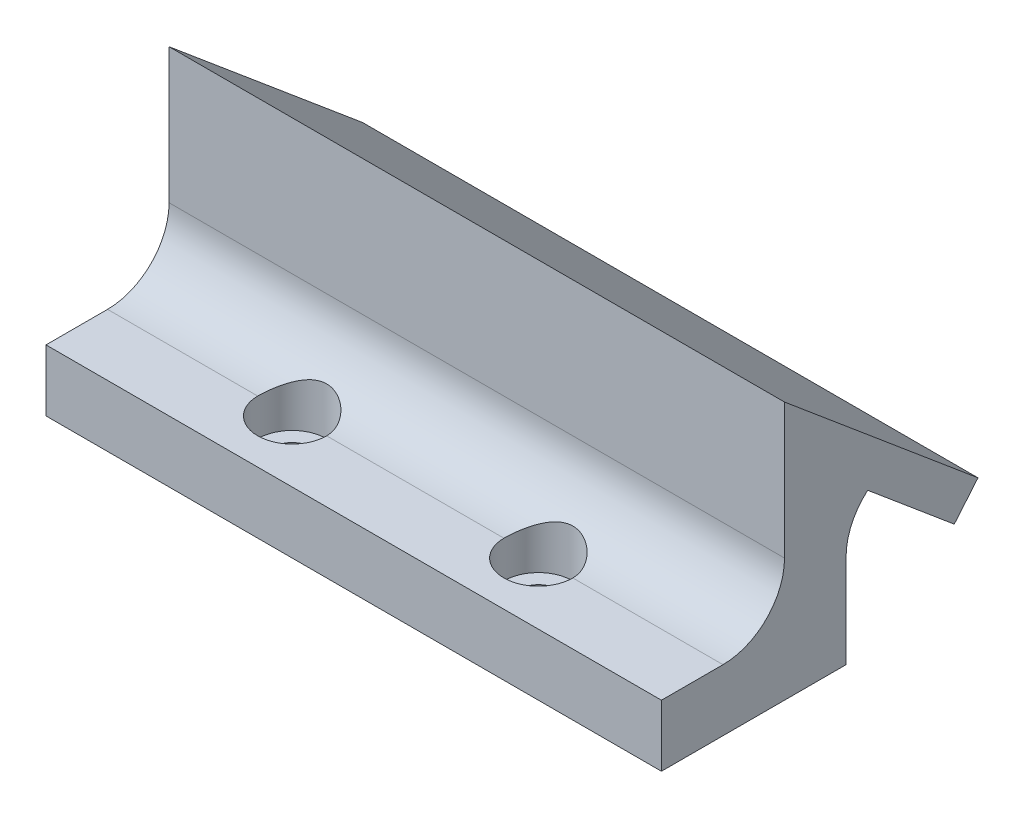
SolidWorks part; units mm, degrees
ref_plane "Alzado" through (0, 0, 0) normal (0, 0, 1) x (1, 0, 0)
ref_plane "Planta" through (0, 0, 0) normal (0, 1, 0) x (1, 0, 0)
ref_plane "Vista lateral" through (0, 0, 0) normal (1, 0, 0) x (0, 0, -1)
sketch "Croquis1" plane through (0, 0, 0) normal (0, 1, 0) x (1, 0, 0)
  line L0 (5, 5) -> (15, 5) construction
  line L1 (0, 0) -> (30, 0)
  line L2 (0, 0) -> (0, 10)
  line L3 (0, 10) -> (30, 10)
  line L4 (30, 0) -> (30, 10)
  line L5 (15, 5) -> (25, 5) construction
  line L6 (15, 5) -> (15, 10) construction
  circle A0 centre (5, 5) radius 1.6
  circle A1 centre (25, 5) radius 1.6
  dimension "D1" = 10
  dimension "D2" = 3.2
  dimension "D3" = 30
  dimension "D4" = 10
  dimension "D5" = 5
extrude "Saliente-Extruir1" add sketch "Croquis1" along normal blind 5
sketch "Croquis2" plane through (0, 5, 0) normal (0, 1, 0) x (1, 0, 0)
  circle A0 centre (5, 5) radius 2.8
  circle A1 centre (25, 5) radius 2.8
  dimension "D1" = 5.6
extrude "Cortar-Extruir1" cut sketch "Croquis2" against normal blind 3
sketch "Croquis6" plane through (0, 0, 0) normal (-1, 0, 0) x (0, 0, 1)
  line L0 (-5, 0) -> (-35, 0) construction
  line L1 (-10, 0) -> (0, 0) construction
  line L2 (-35, 0) -> (-5, 25.173) construction
  line L3 (-5, 25.173) -> (-5, 0) construction
  line L4 (-15, 16.782) -> (-10, 20.9775)
  line L5 (-10, 0) -> (-15, 0)
  line L6 (-10, 5) -> (-10, 16.782)
  line L8 (-15, 0) -> (-15, 12.5865)
  line L9 (-10, 20.9775) -> (-10, 16.782)
  line L10 (-15, 16.782) -> (-20, 12.5865)
  line L11 (-20, 12.5865) -> (-15, 12.5865)
  line L12 (0, 5) -> (0, 0) construction
  line L13 (-10, 5) -> (0, 5) construction
  line L14 (-10, 0) -> (0, 0)
  line L15 (0, 5) -> (0, 0)
  line L16 (-10, 5) -> (0, 5)
  dimension "D1" = 30
  dimension "D2" = 40
  dimension "D3" = 5
extrude "Saliente-Extruir5" add sketch "Croquis6" along normal blind 10
sketch "Croquis7" plane through (0, 0, 0) normal (1, 0, 0) x (0, 0, -1)
  line L6 (10, 20.9775) -> (10, 5)
  line L7 (10, 5) -> (10, 0)
  line L8 (10, 0) -> (15, 0)
  line L9 (15, 0) -> (15, 12.5865)
  line L10 (15, 12.5865) -> (20, 12.5865)
  line L11 (20, 12.5865) -> (10, 20.9775)
  line L12 (10, 20.9775) -> (10, 5)
  line L13 (10, 5) -> (10, 0)
  line L14 (10, 0) -> (15, 0)
  line L15 (15, 0) -> (15, 12.5865)
  line L16 (15, 12.5865) -> (20, 12.5865)
  line L17 (20, 12.5865) -> (10, 20.9775)
  dimension "D1" = 0
extrude "Saliente-Extruir6" add sketch "Croquis7" along normal blind 30
sketch "Croquis8" plane through (30, 0, 0) normal (1, 0, 0) x (0, 0, -1)
  line L4 (0, 0) -> (15, 0)
  line L5 (10, 20.9775) -> (10, 5)
  line L6 (10, 5) -> (0, 5)
  line L7 (0, 5) -> (0, 0)
  line L8 (0, 0) -> (15, 0)
  line L9 (10, 20.9775) -> (10, 5)
  line L10 (10, 5) -> (0, 5)
  line L11 (0, 5) -> (0, 0)
  line L15 (15, 0) -> (15, 12.5865)
  line L16 (15, 0) -> (15, 12.5865)
  line L17 (15, 12.5865) -> (20, 12.5865)
  line L18 (15, 12.5865) -> (20, 12.5865)
  line L19 (20, 12.5865) -> (10, 20.9775)
  line L20 (20, 12.5865) -> (10, 20.9775)
  dimension "D1" = 0
extrude "Saliente-Extruir7" add sketch "Croquis8" along normal blind 10
fillet "Redondeo1" radius 5 1 edges at (15, 5, -10)
fillet "Redondeo2" radius 5 1 edges at (15, 12.5865, -15)
sketch "Croquis9" plane through (-10, 0, 0) normal (-1, 0, 0) x (0, 0, 1)
  line L0 (-20, 12.5865) -> (-25.7172, 7.7892)
  line L1 (-25.7172, 7.7892) -> (-23.7888, 5.4911)
  line L2 (-23.7888, 5.4911) -> (-10, 17.0613)
  line L3 (-10, 10) -> (-10, 20.9775) construction
  line L4 (-10, 17.0613) -> (-10, 20.9775)
  line L5 (-10, 20.9775) -> (-20, 12.5865)
  dimension "D1" = 3
  dimension "D2" = 18
extrude "Saliente-Extruir8" add sketch "Croquis9" against normal up to surface (50 mm away) up to face at (40, 7.6438, -9.375)
